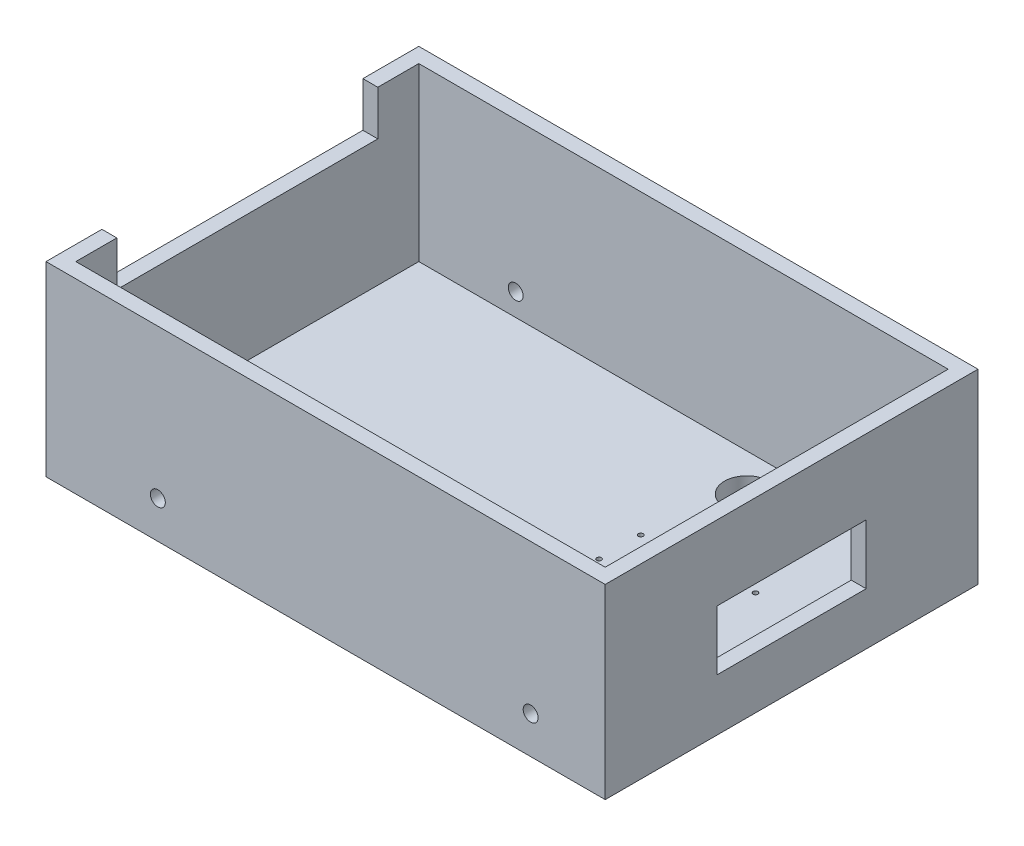
SolidWorks part; units mm, degrees
ref_plane "Front Plane" through (0, 0, 0) normal (0, 0, 1) x (1, 0, 0)
ref_plane "Top Plane" through (0, 0, 0) normal (0, 1, 0) x (1, 0, 0)
ref_plane "Right Plane" through (0, 0, 0) normal (1, 0, 0) x (0, 0, -1)
sketch "Sketch2" plane through (0, 0, 0) normal (0, 1, 0) x (1, 0, 0)
  line L1 (187.5, -125) -> (-187.5, -125)
  line L2 (187.5, -125) -> (187.5, 125)
  line L3 (187.5, 125) -> (-187.5, 125)
  line L4 (-187.5, -125) -> (-187.5, 125)
  line L5 (187.5, -125) -> (-187.5, 125) construction
  line L6 (187.5, 125) -> (-187.5, -125) construction
  point P0 (0, 0)
  dimension "D1" = 250
  dimension "D2" = 375
extrude "Boss-Extrude1" add sketch "Sketch2" along normal blind 125
shell "Shell1" thickness 10 removed face at (0, 125, 0)
sketch "Sketch3" plane through (0, 0, 0) normal (0, 0, 1) x (1, 0, 0)
  line L0 (187.5, 125) -> (187.5, 0) construction
  line L1 (-187.5, 125) -> (-187.5, 0) construction
  line L2 (-187.5, 0) -> (187.5, 0) construction
  circle A0 centre (137.5, 25) radius 5
  circle A1 centre (-112.5, 25) radius 5
  dimension "D1" = 50
  dimension "D2" = 250
  dimension "D3" = 75
  dimension "D4" = 25
  dimension "D5" = 10
extrude "Cut-Extrude1" cut sketch "Sketch3" against normal through all both and the other way through all
sketch "Sketch4" plane through (-187.5, 0, 0) normal (-1, 0, 0) x (0, 0, 1)
  line L0 (-125, 125) -> (125, 125) construction
  line L1 (-87.5, 125) -> (87.5, 125)
  line L2 (-87.5, 125) -> (-87.5, 95)
  line L3 (-87.5, 95) -> (87.5, 95)
  line L4 (87.5, 125) -> (87.5, 95)
  line L5 (-87.5, 125) -> (87.5, 95) construction
  line L6 (-87.5, 95) -> (87.5, 125) construction
  point P4 (0, 110)
  dimension "D1" = 175
  dimension "D2" = 30
extrude "Cut-Extrude2" cut sketch "Sketch4" against normal up to next and the other way through all
hole_wizard "CBORE for M4 SHCS1" positions "Sketch5" profile "Sketch6" counterbore size "M4" standard "ANSI Metric" end condition through all
sketch "Sketch5" plane through (0, 10, 0) normal (0, -1, 0) x (-1, 0, 0)
  line L1 (-187.5, 125) -> (187.5, 125) construction
  line L2 (187.5, -125) -> (-187.5, -125) construction
  line L3 (-112.2, 103.9) -> (-99.2, 103.9) construction
  line L5 (-187.5, -125) -> (-187.5, 125) construction
  point P0 (-99.2, -103.9)
  point P3 (-112.2, -103.9)
  point P6 (-99.2, 103.9)
  point P9 (-112.2, 103.9)
  point P23 (-105.7, 103.9)
  dimension "D1" = 81.8
  dimension "D2" = 13
  dimension "D3" = 21.1
  dimension "D4" = 21.1
sketch "Sketch6" plane through (99.2, 10, 103.9) normal (1, 0, 0) x (0, 0, 1)
  line L0 (0, 0) -> (0, 10)
  line L1 (0, 10) -> (2.25, 10)
  line L3 (2.25, 10) -> (2.25, 4)
  line L4 (2.25, 4) -> (4, 4)
  line L5 (4, 4) -> (4, 0)
  line L7 (4, 0) -> (0, 0)
  line L11 (0, -6.35) -> (0, 107.95) construction
  dimension "Thru Hole Dia." = 4.5
  dimension "Thru Hole Depth" = 10
  dimension "C'Bore Dia." = 8
  dimension "C'Bore Depth" = 4
sketch "Sketch7" plane through (0, 10, 0) normal (0, 1, 0) x (1, 0, 0)
  line L0 (121.7567, 38.2429) -> (55.5156, 38.2429) construction
  line L1 (55.5156, 38.2429) -> (53.1767, 35.8578) construction
  line L2 (53.1767, 35.8578) -> (53.1767, -3.1481) construction
  line L3 (53.1767, -3.1481) -> (55.7167, -4.2545) construction
  line L4 (55.7167, -4.2545) -> (55.7167, -15.0971) construction
  line L5 (55.7167, -15.0971) -> (121.7567, -15.0971) construction
  line L6 (121.7567, -15.0971) -> (121.7567, 38.2429) construction
  line L7 (107.7867, 35.7029) -> (107.7867, -12.5571) construction
  point P0 (127.7856, 35.4929)
  point P2 (127.7856, -12.5571)
  point P5 (55.7167, 30.6229)
  point P8 (55.7167, 2.6829)
  point P25 (106.5167, -12.5571)
  point P27 (107.7867, 35.7029)
  point P39 (107.7867, 11.5729)
  point P40 (121.7567, 11.5729)
  dimension "D1" = 48.05
  dimension "D2" = 27.94
  dimension "D3" = 50.8
  dimension "D4" = 53.34
  dimension "D5" = 45.72
  dimension "D6" = 20
  dimension "D7" = 15.24
  dimension "D8" = 13.97
  dimension "D9" = 50.8
  dimension "D10" = 68.58
  dimension "D11" = 17.78
  dimension "D12" = 66.04
hole_wizard "Ø3.2 (3.2) Diameter Hole1" positions "Sketch7" profile "Sketch8" hole size "Ø3.2" standard "ANSI Metric" end condition up to next
sketch "Sketch8" plane through (127.7856, 10, -35.4929) normal (1, 0, 0) x (0, 0, 1)
  line L0 (0, 0) -> (0, 10)
  line L1 (0, 10) -> (1.6, 10)
  line L2 (1.6, 10) -> (1.6, 0)
  line L5 (1.6, 0) -> (0, 0)
  line L11 (0, -6.35) -> (0, 107.95) construction
  dimension "Thru Hole Dia." = 3.2
  dimension "Thru Hole Depth" = 10
sketch "Sketch9" plane through (187.5, 0, 0) normal (1, 0, 0) x (0, 0, -1)
  line L0 (-125, 0) -> (125, 0) construction
  line L1 (-50, 75) -> (50, 75)
  line L2 (-50, 75) -> (-50, 35)
  line L3 (-50, 35) -> (50, 35)
  line L4 (50, 75) -> (50, 35)
  line L5 (-125, 125) -> (125, 125) construction
  point P4 (0, 0)
  point P7 (0, 35)
  dimension "D1" = 100
  dimension "D2" = 40
  dimension "D3" = 50
extrude "Cut-Extrude3" cut sketch "Sketch9" against normal up to next
sketch "Sketch10" plane through (0, 10, 0) normal (0, 1, 0) x (1, 0, 0)
  line L0 (177.5, 115) -> (-177.5, 115) construction
  line L1 (-177.5, -115) -> (177.5, -115) construction
  line L2 (177.5, -115) -> (177.5, 115) construction
  circle A0 centre (67.5, 90) radius 15
  circle A1 centre (67.5, -90) radius 15
  point P4 (0, 0)
  dimension "D1" = 30
  dimension "D2" = 25
  dimension "D3" = 25
  dimension "D4" = 110
extrude "Cut-Extrude4" cut sketch "Sketch10" against normal through all
